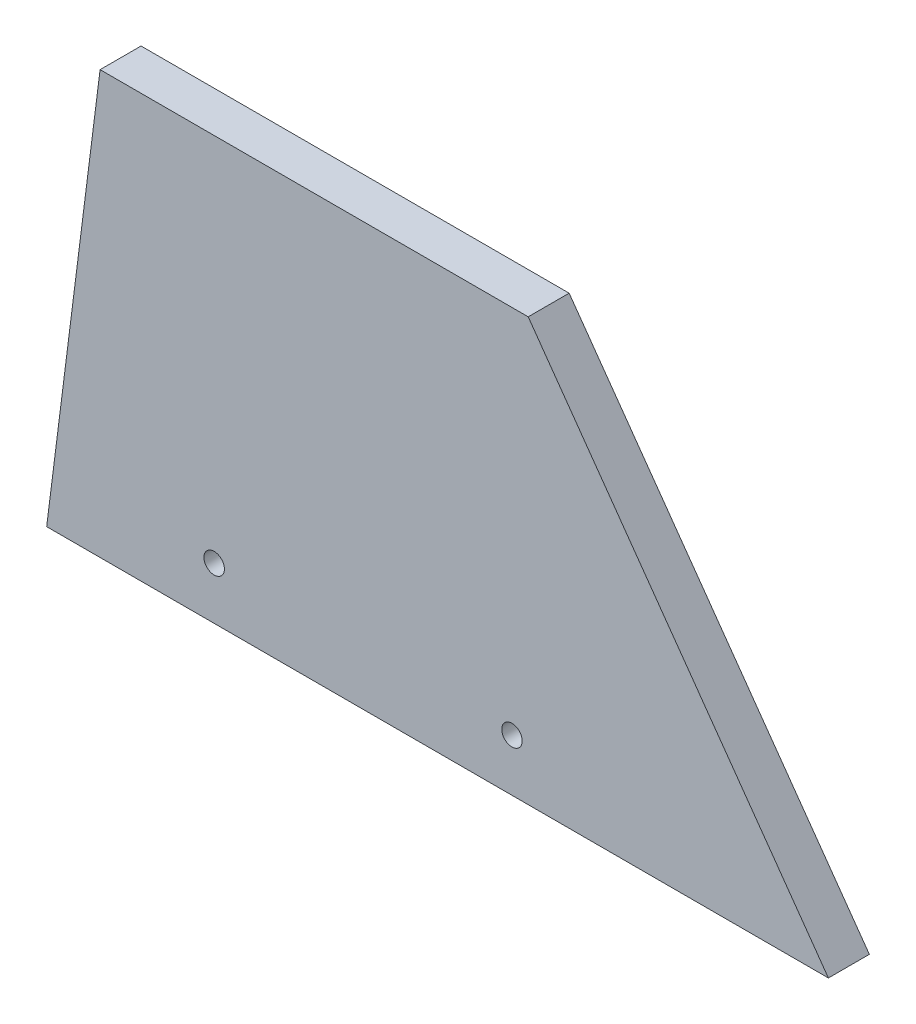
SolidWorks part; units mm, degrees
ref_plane "Plan de face" through (0, 0, 0) normal (0, 0, 1) x (1, 0, 0)
ref_plane "Plan de dessus" through (0, 0, 0) normal (0, 1, 0) x (1, 0, 0)
ref_plane "Plan de droite" through (0, 0, 0) normal (1, 0, 0) x (0, 0, -1)
sketch "Esquisse1" plane through (0, 0, 0) normal (0, 0, 1) x (1, 0, 0)
  line L0 (0, 0) -> (14.357, 113.5)
  line L1 (14.357, 113.5) -> (129.357, 113.5)
  line L2 (129.357, 113.5) -> (210, 0)
  line L3 (210, 0) -> (0, 0)
  line L4 (0, 0) -> (0, 113.5) construction
  line L5 (0, 113.5) -> (14.357, 113.5) construction
  point P5 (29.9685, 70)
  point P7 (14.357, 70)
  point P8 (127.5856, 70)
  dimension "D1" = 210
  dimension "D2" = 115
  dimension "D3" = 113.5
extrude "Boss.-Extru.1" add sketch "Esquisse1" along normal blind 11
sketch "Esquisse2" plane through (0, 0, 0) normal (-0.9921, 0.1255, 0) x (0, 0, 1)
  line L0 (11, 0) -> (0, 0) construction
  arc A0 (11, 0) -> (0, 0) centre (5.5, -76.0012) ccw
  dimension "D1" = 76.2
extrude "Enlèv. mat.-Extru.1" [suppressed] cut sketch "Esquisse2" against normal through all and the other way through all
ref_plane "Plan1" through (0, 0, 5.5) normal (0, 0, 1) x (1, 0, 0)
hole_wizard "Dégagement M51" positions "Esquisse3" profile "Esquisse5" hole size "M5" standard "DIN" end condition through all
sketch "Esquisse3" plane through (0, 0, 11) normal (0, 0, 1) x (1, 0, 0)
  point P0 (125, 14)
  point P3 (45, 14)
sketch "Esquisse5" plane through (125, 14, 11) normal (1, 0, 0) x (0, -1, 0)
  line L0 (0, 0) -> (0, 11)
  line L1 (0, 11) -> (2.75, 11)
  line L2 (2.75, 11) -> (2.75, 0)
  line L5 (2.75, 0) -> (0, 0)
  line L11 (0, -6.35) -> (0, 107.95) construction
  dimension "Diamètre du perçage jusqu'au prochain" = 5.5
  dimension "Profondeur du perçage jusqu'au prochain" = 11
